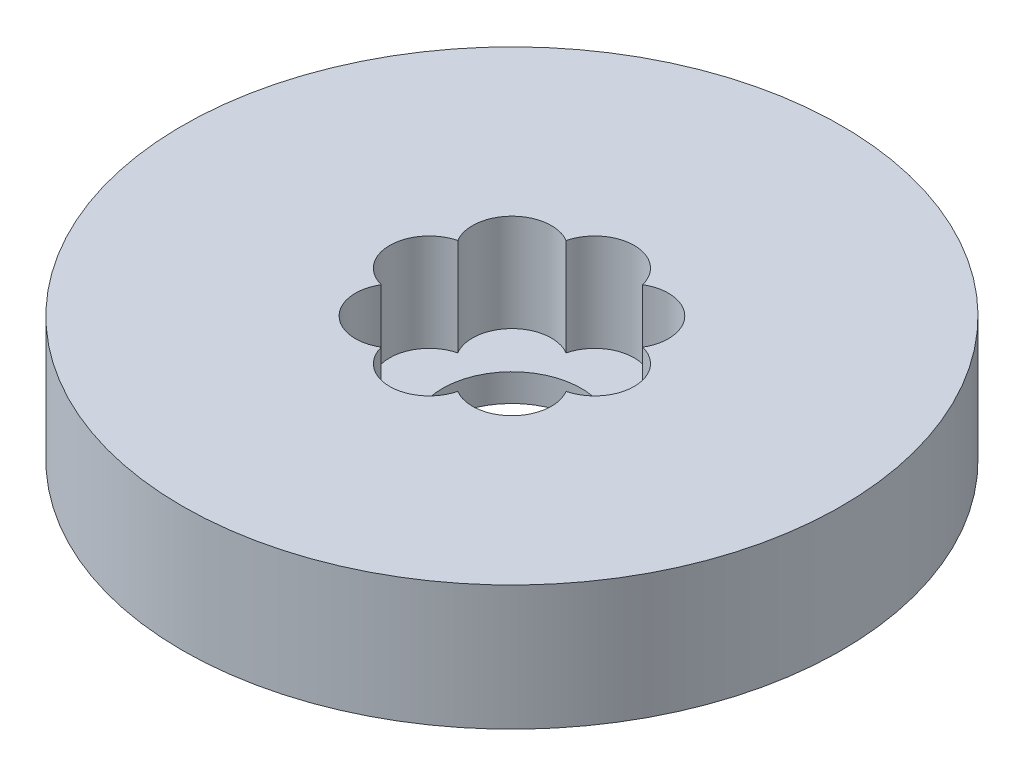
SolidWorks part; units mm, degrees
ref_plane "Front Plane" through (0, 0, 0) normal (0, 0, 1) x (1, 0, 0)
ref_plane "Top Plane" through (0, 0, 0) normal (0, 1, 0) x (1, 0, 0)
ref_plane "Right Plane" through (0, 0, 0) normal (1, 0, 0) x (0, 0, -1)
sketch "Sketch1" plane through (0, 0, 0) normal (0, 1, 0) x (1, 0, 0)
  circle A0 centre (0, 0) radius 47.5
  dimension "FLANGE_OD" = 95
extrude "Boss-Extrude1" add sketch "Sketch1" along normal blind 18
sketch "Sketch2" plane through (0, 0, 0) normal (0, 1, 0) x (1, 0, 0)
  circle A0 centre (0, 0) radius 10
  dimension "BORE_D" = 20
extrude "Cut-Extrude1" cut sketch "Sketch2" along normal through all
sketch "Sketch3" plane through (0, 18, 0) normal (0, 1, 0) x (1, 0, 0)
  circle A0 centre (0, 0) radius 11.9235 construction
  circle A1 centre (-11.9235, 0) radius 5.6939
  dimension "BOLT_D" = 11.3879
  dimension "BOLT_PCD" = 23.8471
extrude "Cut-Extrude2" cut sketch "Sketch3" against normal blind 14.0354
pattern_circular "CirPattern1" count 8 over 360 about axis through (0, 0, 0) along (0, 1, 0) of "Cut-Extrude2"
